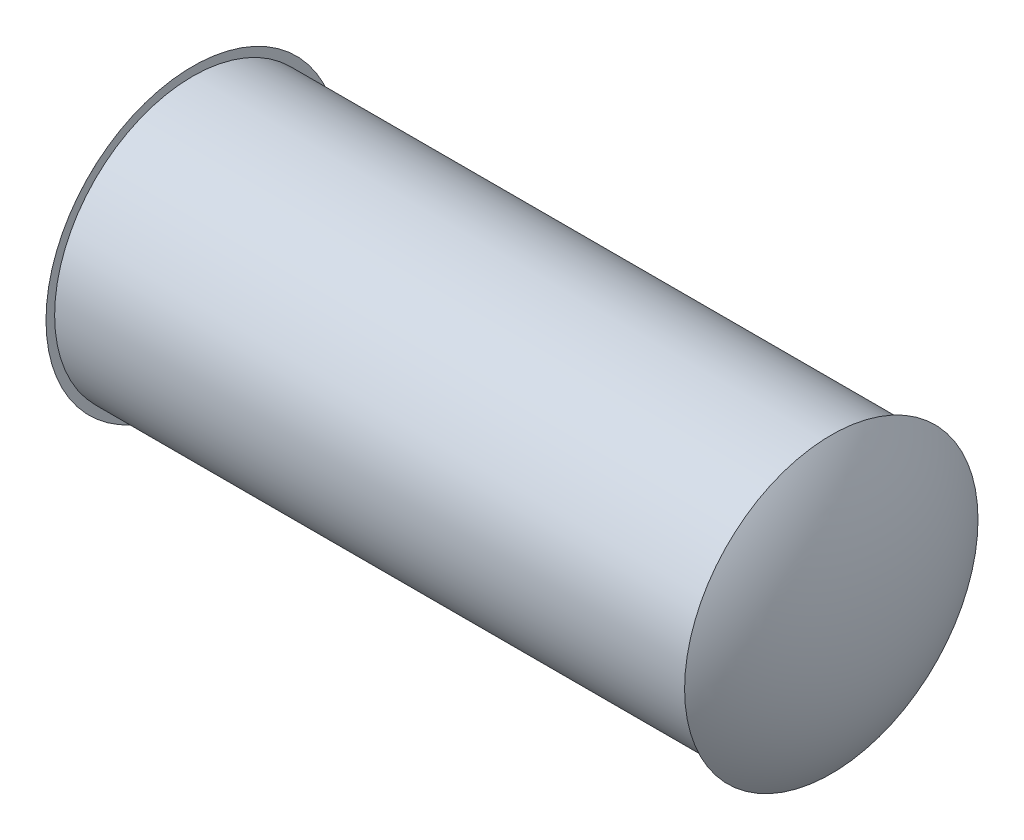
SolidWorks part; units mm, degrees
material "Cast Alloy Steel"
ref_plane "Front Plane" through (0, 0, 0) normal (0, 0, 1) x (1, 0, 0)
ref_plane "Top Plane" through (0, 0, 0) normal (0, 1, 0) x (1, 0, 0)
ref_plane "Right Plane" through (0, 0, 0) normal (1, 0, 0) x (0, 0, -1)
sketch "Sketch1" plane through (0, 0, 0) normal (1, 0, 0) x (0, 0, -1)
  circle A0 centre (0, 0) radius 4.064
  dimension "D1" = 8.128
extrude "Boss-Extrude1" add sketch "Sketch1" along normal blind 9.398 and the other way blind 9.398
sketch "Sketch5" plane through (0, 0, 0) normal (0, 1, 0) x (1, 0, 0)
  line L0 (9.398, 0) -> (9.398, 4.318)
  line L1 (9.398, -4.064) -> (9.398, 4.064) construction
  line L2 (9.398, 0) -> (10.668, 0)
  line L3 (10.668, 0) -> (10.668, -2.1779) construction
  line L4 (9.398, 4.318) -> (7.9267, 4.318) construction
  spline S0 degree 2 poles (9.398, 4.318) (10.668, 2.5954) (10.668, 0) knots 0 0 0 1 1 1
  dimension "D1" = 4.318
  dimension "D2" = 1.27
revolve "Revolve1" add sketch "Sketch5" angle 360 about L2
mirror "Mirror1" about plane through (0, 0, 0) normal (1, 0, 0) of "Revolve1"
